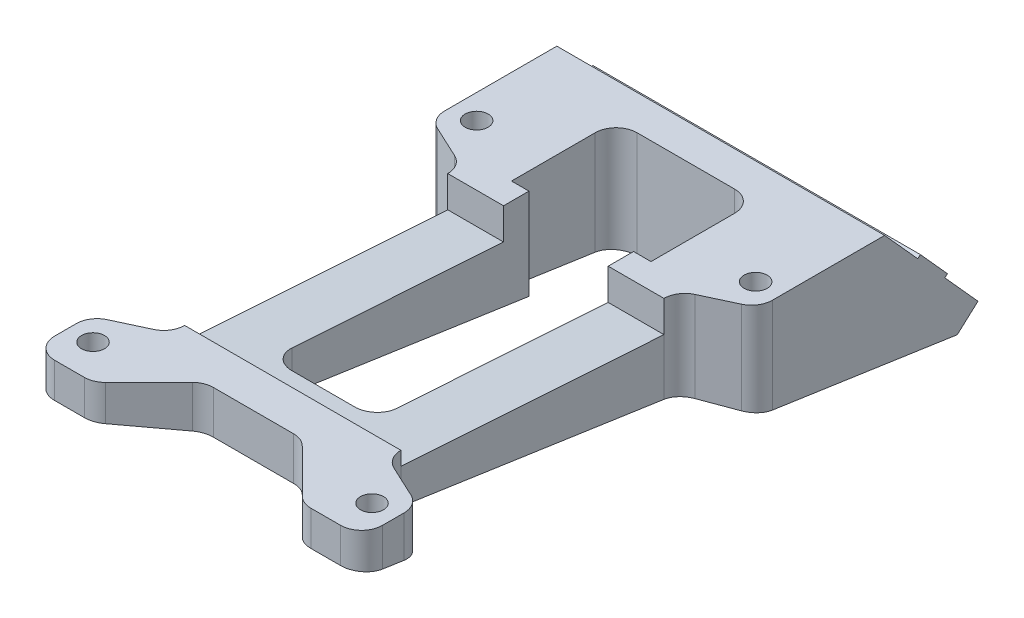
SolidWorks part; units mm, degrees
ref_plane "前视基准面" through (0, 0, 0) normal (0, 0, 1) x (1, 0, 0)
ref_plane "上视基准面" through (0, 0, 0) normal (0, 1, 0) x (1, 0, 0)
ref_plane "右视基准面" through (0, 0, 0) normal (1, 0, 0) x (0, 0, -1)
sketch "草图2" plane through (0, 0, 0) normal (0, 1, 0) x (1, 0, 0)
  line L0 (0, 0) -> (23.5, 0)
  line L1 (23.5, 0) -> (23.5, -14)
  line L4 (23.5, -75) -> (0, -75)
  line L5 (0, -75) -> (0, 0)
  line L6 (23.5, -14) -> (23.5, -75)
  dimension "D1" = 23.5
  dimension "D2" = 75
  dimension "D3" = 23.5
  dimension "D4" = 23.5
  dimension "D6" = 61
extrude "凸台-拉伸2" add sketch "草图2" along normal blind 5
mirror "镜向1" about plane through (0, 5, 75) normal (1, 0, 0) of "凸台-拉伸2"
sketch "草图3" plane through (0, 5, 0) normal (0, 1, 0) x (1, 0, 0)
  line L0 (-41.875, -15) -> (42.0058, -15) construction
  line L1 (-48.5488, -70) -> (45.2773, -70) construction
  line L2 (-20, 7.7517) -> (-20, -80.1072) construction
  line L3 (20, 7.7517) -> (20, -77.5947) construction
  line L4 (-23.5, -75) -> (23.5, -75) construction
  circle A0 centre (-20, -15) radius 1.65
  circle A1 centre (20, -15) radius 1.65
  circle A2 centre (-20, -70) radius 1.65
  circle A3 centre (20, -70) radius 1.65
  point P10 (0, -75)
  dimension "D5" = 3.3
  dimension "D1" = 5
  dimension "D2" = 55
  dimension "D3" = 40
  dimension "D4" = 20
extrude "切除-拉伸1" cut sketch "草图3" against normal through all
sketch "草图5" plane through (0, 0, 0) normal (1, 0, 0) x (0, 0, -1)
  line L0 (-75, 0) -> (10.41, -12.5394)
  line L1 (10.41, -12.5394) -> (13.3826, -9.8629)
  line L2 (13.3826, -9.8629) -> (0, 5)
  line L3 (0, 5) -> (0, 0) construction
  line L4 (-75, 0) -> (0, 0) construction
  line L5 (0, 5) -> (0, 0)
  line L6 (-75, 0) -> (0, 0)
  line L7 (4.7508, -0.2763) -> (8.6318, -4.5866)
  line L8 (4.7508, -0.2763) -> (5.1224, 0.0582)
  line L9 (8.6318, -4.5866) -> (9.0034, -4.252)
  line L10 (5.1224, 0.0582) -> (9.0034, -4.252)
  line L11 (7.0629, -2.0969) -> (3.8382, -5.0004) construction
  dimension "D1" = 20
  dimension "D2" = 4
  dimension "D3" = 42
  dimension "D4" = 10
  dimension "D5" = 5.8
  dimension "D6" = 0.5
extrude "凸台-拉伸3" add sketch "草图5" along normal mid plane 47 contours L6 L0 L1 L2 L7 L5 | L11 L10 L8 L7 | L10 L11 L2 L9 region at (0, -4.2198, 18.1192) region at (0, -3.3417, -7.8473) region at (0, -1.1866, -5.9069)
sketch "草图6" plane through (0, 2.5732, -2.8579) normal (0, 0.6691, -0.7431) x (1, 0, 0)
  line L0 (-23.5, 6.2843) -> (23.5, 6.2843) construction
  line L1 (-23.5, 3.3843) -> (-23.5, 9.1843) construction
  line L2 (23.5, 3.3843) -> (23.5, 9.1843) construction
  line L3 (-13.5, 9.1843) -> (-13.5, 3.3843) construction
  line L4 (23.5, 9.1843) -> (-23.5, 9.1843) construction
  line L5 (23.5, 3.3843) -> (-23.5, 3.3843) construction
  line L6 (13.5, 9.1843) -> (13.5, 3.3843) construction
  line L7 (23.5, 9.1843) -> (-23.5, 9.1843) construction
  line L8 (23.5, 3.3843) -> (-23.5, 3.3843) construction
  circle A0 centre (-13.5, 6.2843) radius 2.6
  circle A1 centre (13.5, 6.2843) radius 2.6
  dimension "D3" = 5.2
  dimension "D1" = 10
  dimension "D2" = 10
extrude "切除-拉伸3" cut sketch "草图6" against normal through all
sketch "草图7" plane through (0, 2.5732, -2.8579) normal (0, 0.6691, -0.7431) x (1, 0, 0)
  circle A0 centre (-13.5, 6.2843) radius 4.5
  circle A1 centre (13.5, 6.2843) radius 4.5
  dimension "D1" = 9
extrude "切除-拉伸4" cut sketch "草图7" against normal up to next from offset 5 offset against normal yes
sketch "草图8" plane through (0, 5, 0) normal (0, -1, 0) x (1, 0, 0)
  circle A0 centre (-20, 15) radius 3
  circle A1 centre (20, 15) radius 3
  circle A2 centre (20, 70) radius 3
  circle A3 centre (-20, 70) radius 3
  dimension "D1" = 6
extrude "切除-拉伸5" cut sketch "草图8" along normal up to next from offset 3
sketch "草图4" plane through (0, 5, 0) normal (0, 1, 0) x (1, 0, 0)
  line L0 (-23.5, -75) -> (23.5, -75) construction
  line L1 (-7.5, -5) -> (7.5, -5)
  line L2 (-7.5, -5) -> (-7.5, -57)
  line L3 (-7.5, -57) -> (7.5, -57)
  line L4 (7.5, -5) -> (7.5, -57)
  line L5 (-15, -75) -> (-7, -67)
  line L6 (-7, -67) -> (7, -67)
  line L7 (7, -67) -> (15, -75)
  line L8 (15, -75) -> (-15, -75)
  line L9 (-23.5, -67) -> (-15.5, -63.2695)
  line L10 (-23.5, -75) -> (-23.5, 0) construction
  line L11 (-15.5, -63.2695) -> (-15.5, -21.7305)
  line L12 (-15.5, -21.7305) -> (-23.5, -18)
  line L13 (-23.5, -18) -> (-23.5, -67)
  line L14 (-23.5, -75) -> (23.5, -75) construction
  line L15 (23.5, 0) -> (-23.5, 0) construction
  line L16 (0, 0) -> (0, -5.79) construction
  line L17 (15.5, -21.7305) -> (23.5, -18)
  line L18 (15.5, -63.2695) -> (15.5, -21.7305)
  line L19 (23.5, -67) -> (15.5, -63.2695)
  line L20 (23.5, -18) -> (23.5, -67)
  line L22 (-10, -5) -> (10, -5)
  line L23 (-10, -5) -> (-10, -20)
  line L24 (-10, -20) -> (10, -20)
  line L25 (10, -5) -> (10, -20)
  point P6 (0, -75)
  point P10 (0, -75)
  point P33 (0, -5)
  line M9 (-23.5, 0) -> (-23.5, -75)
  line M15 (-23.5, -75) -> (23.5, -75)
  line M28 (23.5, -75) -> (23.5, 0)
  dimension "D1" = 18
  dimension "D2" = 52
  dimension "D3" = 15
  dimension "D4" = 7.5
  dimension "D5" = 30
  dimension "D6" = 8
  dimension "D7" = 45
  dimension "D8" = 45
  dimension "D9" = 8
  dimension "D10" = 18
  dimension "D11" = 8
  dimension "D12" = 65
  dimension "D13" = 65
  dimension "D14" = 20
  dimension "D15" = 15
extrude "切除-拉伸2" cut sketch "草图4" against normal through all contours L11 L12 L9 M9 | L19 L17 L18 M28 | L7 L6 L5 M15 | L24 L2 L3 L4 | L24 L25 L22 L23 region at (0, 5, 38.5) region at (19.6099, 5, 42.5) region at (0, 5, 71.4848) region at (-19.6099, 5, 42.5)
fillet "圆角1" radius 3 18 edges at (7.5, 1.1787, 57) (-7.5, 1.1787, 57) (23.5, -1.6842, 18) (15.5, -1.4104, 21.7305) (15.5, 1.6389, 63.2695) (23.5, 1.9127, 67) (23.5, 2.5, 75) (15, 2.5, 75) (7, 1.9127, 67) (-7, 1.9127, 67) (-15, 2.5, 75) (-23.5, 2.5, 75) (-23.5, 1.9127, 67) (-15.5, 1.6389, 63.2695) (-15.5, -1.4104, 21.7305) (-23.5, -1.6842, 18) (10, -2.0762, 5) (-10, -2.0762, 5)
sketch "草图9" plane through (0, 5, 0) normal (0, 1, 0) x (1, 0, 0)
  line L0 (-15.5, -61.3583) -> (-15.5, -23.6417) construction
  line L1 (-15.5, -23.6417) -> (15.5, -23.6417)
  line L2 (-15.5, -23.6417) -> (-15.5, -61.3583)
  line L3 (-15.5, -61.3583) -> (15.5, -61.3583)
  line L4 (15.5, -23.6417) -> (15.5, -61.3583)
  line L5 (15.5, -61.3583) -> (15.5, -23.6417) construction
  arc A0 (15.5, -61.3583) -> (17.2321, -64.0773) centre (18.5, -61.3583) ccw construction
extrude "切除-拉伸6" [suppressed] cut sketch "草图9" against normal blind 2
sketch "草图10" plane through (-15.5, 0, 0) normal (-1, 0, 0) x (0, 0, 1)
  line L0 (23.6417, 5) -> (23.6417, 0.5)
  line L1 (23.6417, 5) -> (23.6417, -7.5401) construction
  line L2 (23.6417, 0.5) -> (61.3583, 3)
  line L3 (61.3583, -2.0028) -> (61.3583, 5) construction
  line L4 (61.3583, 3) -> (61.3583, 5)
  line L5 (61.3583, 5) -> (23.6417, 5)
  dimension "D1" = 4.5
  dimension "D2" = 2
extrude "切除-拉伸7" cut sketch "草图10" against normal through all
